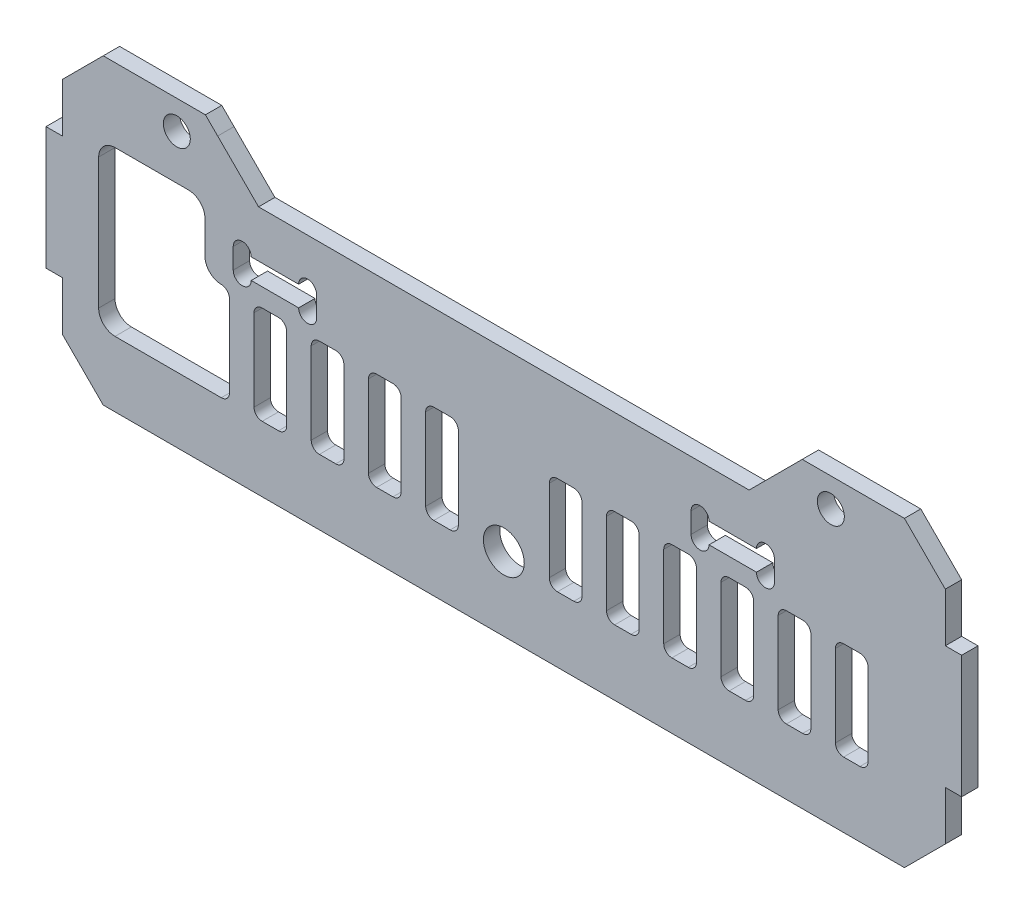
SolidWorks part; units mm, degrees
material "A-玻璃纤维"
ref_plane "前视基准面" through (0, 0, 0) normal (0, 0, 1) x (1, 0, 0)
ref_plane "上视基准面" through (0, 0, 0) normal (0, 1, 0) x (1, 0, 0)
ref_plane "右视基准面" through (0, 0, 0) normal (1, 0, 0) x (0, 0, -1)
sketch "草图1" plane through (0, 0, 0) normal (0, 0, 1) x (1, 0, 0)
  line L1 (52.5, -21.5) -> (-52.5, -21.5)
  line L2 (52.5, -21.5) -> (52.5, 21.5)
  line L3 (52.5, 21.5) -> (-52.5, 21.5)
  line L4 (-52.5, -21.5) -> (-52.5, 21.5)
  line L5 (52.5, -21.5) -> (-52.5, 21.5) construction
  line L6 (52.5, 21.5) -> (-52.5, -21.5) construction
  point P0 (0, 0)
  dimension "D1" = 43
  dimension "D2" = 105
extrude "凸台-拉伸1" add sketch "草图1" along normal blind 2
sketch "草图2" plane through (0, 0, 2) normal (0, 0, 1) x (1, 0, 0)
  line L0 (-52.5, -21.5) -> (52.5, -21.5) construction
  circle A0 centre (0, -6.5) radius 2.5
  dimension "D1" = 5
  dimension "D2" = 15
extrude "切除-拉伸1" cut sketch "草图2" against normal blind 2
sketch "草图3" plane through (0, 0, 2) normal (0, 0, 1) x (1, 0, 0)
  line L0 (0, -6.5) -> (0, 30.8618) construction
  line L1 (-52.5, -21.5) -> (52.5, -21.5) construction
  circle A0 centre (-40, -18.5) radius 1.65
  circle A1 centre (-40, 13.5) radius 1.65
  circle A2 centre (40, 13.5) radius 1.65
  circle A3 centre (40, -18.5) radius 1.65
  dimension "D1" = 3.3
  dimension "D2" = 3.3
  dimension "D4" = 32
  dimension "D5" = 3
  dimension "D3" = 40
extrude "切除-拉伸2" cut sketch "草图3" against normal blind 2
sketch "草图4" plane through (0, 0, 2) normal (0, 0, 1) x (1, 0, 0)
  line L0 (-2.5, -6.5) -> (2.5, -6.5) construction
  line L1 (-6.5592, -7.5) -> (-8.5592, -7.5)
  line L2 (-5.5592, -6.5) -> (-5.5592, 3.5)
  line L3 (-6.5592, 4.5) -> (-8.5592, 4.5)
  line L4 (-9.5592, -6.5) -> (-9.5592, 3.5)
  line L5 (-5.5592, -7.5) -> (-9.5592, 4.5) construction
  line L6 (-5.5592, 4.5) -> (-9.5592, -7.5) construction
  line L7 (-12.5592, -6.5) -> (-12.5592, 3.5)
  line L8 (-13.5592, -7.5) -> (-15.5592, -7.5)
  line L9 (-16.5592, -6.5) -> (-16.5592, 3.5)
  line L10 (-13.5592, 4.5) -> (-15.5592, 4.5)
  line L11 (-19.5592, -6.5) -> (-19.5592, 3.5)
  line L12 (-20.5592, -7.5) -> (-22.5592, -7.5)
  line L13 (-23.5592, -6.5) -> (-23.5592, 3.5)
  line L14 (-20.5592, 4.5) -> (-22.5592, 4.5)
  line L15 (-26.5592, -6.5) -> (-26.5592, 3.5)
  line L16 (-27.5592, -7.5) -> (-29.5592, -7.5)
  line L17 (-30.5592, -6.5) -> (-30.5592, 3.5)
  line L18 (-27.5592, 4.5) -> (-29.5592, 4.5)
  line L19 (-33.5592, -6.5) -> (-33.5592, 3.5)
  line L20 (-34.5592, -7.5) -> (-36.5592, -7.5)
  line L21 (-37.5592, -6.5) -> (-37.5592, 3.5)
  line L22 (-34.5592, 4.5) -> (-36.5592, 4.5)
  line L23 (-40.5592, -6.5) -> (-40.5592, 3.5)
  line L24 (-41.5592, -7.5) -> (-43.5592, -7.5)
  line L25 (-44.5592, -6.5) -> (-44.5592, 3.5)
  line L26 (-41.5592, 4.5) -> (-43.5592, 4.5)
  line L27 (0, -6.5) -> (0, 35.5966) construction
  line L28 (5.5592, 4.5) -> (9.5592, -7.5) construction
  line L29 (5.5592, -7.5) -> (9.5592, 4.5) construction
  line L30 (41.5592, 4.5) -> (43.5592, 4.5)
  line L31 (44.5592, -6.5) -> (44.5592, 3.5)
  line L32 (41.5592, -7.5) -> (43.5592, -7.5)
  line L33 (40.5592, -6.5) -> (40.5592, 3.5)
  line L34 (34.5592, 4.5) -> (36.5592, 4.5)
  line L35 (37.5592, -6.5) -> (37.5592, 3.5)
  line L36 (34.5592, -7.5) -> (36.5592, -7.5)
  line L37 (33.5592, -6.5) -> (33.5592, 3.5)
  line L38 (27.5592, 4.5) -> (29.5592, 4.5)
  line L39 (30.5592, -6.5) -> (30.5592, 3.5)
  line L40 (27.5592, -7.5) -> (29.5592, -7.5)
  line L41 (26.5592, -6.5) -> (26.5592, 3.5)
  line L42 (20.5592, 4.5) -> (22.5592, 4.5)
  line L43 (23.5592, -6.5) -> (23.5592, 3.5)
  line L44 (20.5592, -7.5) -> (22.5592, -7.5)
  line L45 (19.5592, -6.5) -> (19.5592, 3.5)
  line L46 (13.5592, 4.5) -> (15.5592, 4.5)
  line L47 (16.5592, -6.5) -> (16.5592, 3.5)
  line L48 (13.5592, -7.5) -> (15.5592, -7.5)
  line L49 (12.5592, -6.5) -> (12.5592, 3.5)
  line L50 (9.5592, -6.5) -> (9.5592, 3.5)
  line L51 (6.5592, 4.5) -> (8.5592, 4.5)
  line L52 (5.5592, -6.5) -> (5.5592, 3.5)
  line L53 (6.5592, -7.5) -> (8.5592, -7.5)
  circle A0 centre (0, -6.5) radius 2.5 construction
  arc A1 (-8.5592, -7.5) -> (-9.5592, -6.5) centre (-8.5592, -6.5) cw
  arc A2 (-6.5592, -7.5) -> (-5.5592, -6.5) centre (-6.5592, -6.5) ccw
  arc A3 (-5.5592, 3.5) -> (-6.5592, 4.5) centre (-6.5592, 3.5) ccw
  arc A4 (-8.5592, 4.5) -> (-9.5592, 3.5) centre (-8.5592, 3.5) ccw
  arc A5 (-12.5592, 3.5) -> (-13.5592, 4.5) centre (-13.5592, 3.5) ccw
  arc A6 (-13.5592, -7.5) -> (-12.5592, -6.5) centre (-13.5592, -6.5) ccw
  arc A7 (-15.5592, -7.5) -> (-16.5592, -6.5) centre (-15.5592, -6.5) cw
  arc A8 (-15.5592, 4.5) -> (-16.5592, 3.5) centre (-15.5592, 3.5) ccw
  arc A9 (-19.5592, 3.5) -> (-20.5592, 4.5) centre (-20.5592, 3.5) ccw
  arc A10 (-20.5592, -7.5) -> (-19.5592, -6.5) centre (-20.5592, -6.5) ccw
  arc A11 (-22.5592, -7.5) -> (-23.5592, -6.5) centre (-22.5592, -6.5) cw
  arc A12 (-22.5592, 4.5) -> (-23.5592, 3.5) centre (-22.5592, 3.5) ccw
  arc A13 (-26.5592, 3.5) -> (-27.5592, 4.5) centre (-27.5592, 3.5) ccw
  arc A14 (-27.5592, -7.5) -> (-26.5592, -6.5) centre (-27.5592, -6.5) ccw
  arc A15 (-29.5592, -7.5) -> (-30.5592, -6.5) centre (-29.5592, -6.5) cw
  arc A16 (-29.5592, 4.5) -> (-30.5592, 3.5) centre (-29.5592, 3.5) ccw
  arc A17 (-33.5592, 3.5) -> (-34.5592, 4.5) centre (-34.5592, 3.5) ccw
  arc A18 (-34.5592, -7.5) -> (-33.5592, -6.5) centre (-34.5592, -6.5) ccw
  arc A19 (-36.5592, -7.5) -> (-37.5592, -6.5) centre (-36.5592, -6.5) cw
  arc A20 (-36.5592, 4.5) -> (-37.5592, 3.5) centre (-36.5592, 3.5) ccw
  arc A21 (-40.5592, 3.5) -> (-41.5592, 4.5) centre (-41.5592, 3.5) ccw
  arc A22 (-41.5592, -7.5) -> (-40.5592, -6.5) centre (-41.5592, -6.5) ccw
  arc A23 (-43.5592, -7.5) -> (-44.5592, -6.5) centre (-43.5592, -6.5) cw
  arc A24 (-43.5592, 4.5) -> (-44.5592, 3.5) centre (-43.5592, 3.5) ccw
  arc A25 (43.5592, 4.5) -> (44.5592, 3.5) centre (43.5592, 3.5) cw
  arc A26 (43.5592, -7.5) -> (44.5592, -6.5) centre (43.5592, -6.5) ccw
  arc A27 (41.5592, -7.5) -> (40.5592, -6.5) centre (41.5592, -6.5) cw
  arc A28 (40.5592, 3.5) -> (41.5592, 4.5) centre (41.5592, 3.5) cw
  arc A29 (36.5592, 4.5) -> (37.5592, 3.5) centre (36.5592, 3.5) cw
  arc A30 (36.5592, -7.5) -> (37.5592, -6.5) centre (36.5592, -6.5) ccw
  arc A31 (34.5592, -7.5) -> (33.5592, -6.5) centre (34.5592, -6.5) cw
  arc A32 (33.5592, 3.5) -> (34.5592, 4.5) centre (34.5592, 3.5) cw
  arc A33 (29.5592, 4.5) -> (30.5592, 3.5) centre (29.5592, 3.5) cw
  arc A34 (29.5592, -7.5) -> (30.5592, -6.5) centre (29.5592, -6.5) ccw
  arc A35 (27.5592, -7.5) -> (26.5592, -6.5) centre (27.5592, -6.5) cw
  arc A36 (26.5592, 3.5) -> (27.5592, 4.5) centre (27.5592, 3.5) cw
  arc A37 (22.5592, 4.5) -> (23.5592, 3.5) centre (22.5592, 3.5) cw
  arc A38 (22.5592, -7.5) -> (23.5592, -6.5) centre (22.5592, -6.5) ccw
  arc A39 (20.5592, -7.5) -> (19.5592, -6.5) centre (20.5592, -6.5) cw
  arc A40 (19.5592, 3.5) -> (20.5592, 4.5) centre (20.5592, 3.5) cw
  arc A41 (15.5592, 4.5) -> (16.5592, 3.5) centre (15.5592, 3.5) cw
  arc A42 (15.5592, -7.5) -> (16.5592, -6.5) centre (15.5592, -6.5) ccw
  arc A43 (13.5592, -7.5) -> (12.5592, -6.5) centre (13.5592, -6.5) cw
  arc A44 (12.5592, 3.5) -> (13.5592, 4.5) centre (13.5592, 3.5) cw
  arc A45 (8.5592, 4.5) -> (9.5592, 3.5) centre (8.5592, 3.5) cw
  arc A46 (5.5592, 3.5) -> (6.5592, 4.5) centre (6.5592, 3.5) cw
  arc A47 (6.5592, -7.5) -> (5.5592, -6.5) centre (6.5592, -6.5) cw
  arc A48 (8.5592, -7.5) -> (9.5592, -6.5) centre (8.5592, -6.5) ccw
  point P0 (-7.5592, -1.5)
  point P161 (7.5592, -1.5)
  dimension "D5" = 1
  dimension "D1" = 12
  dimension "D2" = 4
  dimension "D3" = 4
  dimension "D4" = 5
  dimension "D6" = 6
extrude "切除-拉伸3" cut sketch "草图4" against normal blind 2
sketch "草图5" plane through (0, 0, 2) normal (0, 0, 1) x (1, 0, 0)
  line L0 (-28, 8) -> (-28, 13.9357) construction
  line L1 (-25.1, 6.75) -> (-30.9, 6.75)
  line L2 (-22.9, 6.75) -> (-22.9, 9.25)
  line L3 (-25.1, 9.25) -> (-30.9, 9.25)
  line L4 (-33.1, 6.75) -> (-33.1, 9.25)
  line L5 (-22.9, 6.75) -> (-33.1, 9.25) construction
  line L6 (-22.9, 9.25) -> (-33.1, 6.75) construction
  line L11 (0, 0) -> (0, 36.2571) construction
  line L12 (22.9, 6.75) -> (22.9, 9.25)
  line L13 (25.1, 9.25) -> (30.9, 9.25)
  line L14 (33.1, 6.75) -> (33.1, 9.25)
  line L15 (25.1, 6.75) -> (30.9, 6.75)
  arc A0 (-30.9, 9.25) -> (-33.1, 9.25) centre (-32, 9.25) ccw
  arc A1 (-33.1, 6.75) -> (-30.9, 6.75) centre (-32, 6.75) ccw
  arc A2 (-22.9, 6.75) -> (-25.1, 6.75) centre (-24, 6.75) cw
  arc A3 (-25.1, 9.25) -> (-22.9, 9.25) centre (-24, 9.25) cw
  arc A4 (22.9, 6.75) -> (25.1, 6.75) centre (24, 6.75) ccw
  arc A5 (25.1, 9.25) -> (22.9, 9.25) centre (24, 9.25) ccw
  arc A6 (30.9, 9.25) -> (33.1, 9.25) centre (32, 9.25) cw
  arc A7 (33.1, 6.75) -> (30.9, 6.75) centre (32, 6.75) cw
  point P0 (-28, 8)
  point P5 (28, 8)
  dimension "D8" = 2.2
  dimension "D9" = 2.2
  dimension "D1" = 2.5
  dimension "D2" = 10.2
  dimension "D5" = 28
  dimension "D6" = 28
  dimension "D7" = 8
extrude "切除-拉伸4" cut sketch "草图5" against normal blind 2
sketch "草图6" plane through (0, 0, 2) normal (0, 0, 1) x (1, 0, 0)
  line L0 (-52.5, 21.5) -> (-52.5, -21.5) construction
  line L1 (52.5, -21.5) -> (52.5, 21.5) construction
  line L2 (-52.5, -21.5) -> (52.5, -21.5) construction
  circle A0 centre (-49.5, 3.5) radius 1.65
  circle A1 centre (-49.5, -11.5) radius 1.65
  circle A2 centre (49.5, 3.5) radius 1.65
  circle A3 centre (49.5, -11.5) radius 1.65
  dimension "D1" = 3.3
  dimension "D2" = 3.3
  dimension "D3" = 3.3
  dimension "D4" = 3.3
  dimension "D5" = 3
  dimension "D6" = 3
  dimension "D7" = 15
  dimension "D8" = 10
sketch "草图7" plane through (0, 0, 2) normal (0, 0, 1) x (1, 0, 0)
  line L0 (52.5, 21.5) -> (-52.5, 21.5) construction
  line L1 (-53.8951, 21.5) -> (65.5252, 21.5)
  line L2 (-53.8951, 21.5) -> (-53.8951, 11.5)
  line L3 (-53.8951, 11.5) -> (65.5252, 11.5)
  line L4 (65.5252, 21.5) -> (65.5252, 11.5)
  dimension "D1" = 10
extrude "切除-拉伸6" cut sketch "草图7" against normal blind 2
sketch "草图8" plane through (0, 0, 2) normal (0, 0, 1) x (1, 0, 0)
  line L1 (-52.5, 11.5) -> (-48.39, 11.5)
  line L2 (-52.5, 11.5) -> (-52.5, -21.5)
  line L3 (-52.5, -21.5) -> (-48.39, -21.5)
  line L4 (-48.39, 11.5) -> (-48.39, -21.5)
  line L5 (-52.5, -21.5) -> (52.5, -21.5) construction
  line L7 (52.5, 11.5) -> (48.39, 11.5)
  line L8 (52.5, 11.5) -> (52.5, -21.5)
  line L9 (52.5, -21.5) -> (48.39, -21.5)
  line L10 (48.39, 11.5) -> (48.39, -21.5)
  dimension "D1" = 33
  dimension "D2" = 4.11
  dimension "D3" = 33
  dimension "D4" = 4.11
extrude "切除-拉伸7" cut sketch "草图8" against normal blind 2
sketch "草图11" plane through (0, 0, 2) normal (0, 0, 1) x (1, 0, 0)
  line L0 (-48.39, -21.5) -> (-48.39, 11.5) construction
  line L1 (-48.39, 8.5) -> (-50.39, 8.5)
  line L2 (-48.39, 8.5) -> (-48.39, -6.5)
  line L3 (-48.39, -6.5) -> (-50.39, -6.5)
  line L4 (-50.39, 8.5) -> (-50.39, -6.5)
  line L5 (48.39, 11.5) -> (48.39, -21.5) construction
  line L6 (48.39, 8.5) -> (50.39, 8.5)
  line L7 (48.39, 8.5) -> (48.39, -6.5)
  line L8 (48.39, -6.5) -> (50.39, -6.5)
  line L9 (50.39, 8.5) -> (50.39, -6.5)
  line L10 (-48.39, 11.5) -> (48.39, 11.5) construction
  dimension "D1" = 15
  dimension "D2" = 2
  dimension "D3" = 15
  dimension "D4" = 2
  dimension "D9" = 3
  dimension "D11" = 3
extrude "凸台-拉伸2" add sketch "草图11" against normal up to vertex (2 mm away) up to point (22.9, 9.25, 0)
sketch "草图13" plane through (0, 0, 0) normal (0, 0, -1) x (-1, 0, 0)
  line L0 (48.39, -21.5) -> (48.39, -6.5) construction
  line L1 (-48.39, -21.5) -> (48.39, -21.5)
  line L2 (-48.39, -21.5) -> (-48.39, -15.5)
  line L3 (-48.39, -15.5) -> (48.39, -15.5)
  line L4 (48.39, -21.5) -> (48.39, -15.5)
  dimension "D1" = 6
extrude "切除-拉伸8" cut sketch "草图13" against normal blind 2
sketch "草图14" plane through (0, 0, 0) normal (0, 0, -1) x (-1, 0, 0)
  line L0 (48.39, 11.5) -> (-48.39, 11.5) construction
  line L1 (48.39, 21.5) -> (-48.39, 21.5)
  line L2 (48.39, 21.5) -> (48.39, 11.5)
  line L3 (48.39, 11.5) -> (-48.39, 11.5)
  line L4 (-48.39, 21.5) -> (-48.39, 11.5)
  line L5 (48.39, 21.5) -> (-48.39, 11.5) construction
  line L6 (48.39, 11.5) -> (-48.39, 21.5) construction
  line L7 (-48.39, 11.5) -> (-48.39, 8.5) construction
  point P0 (0, 16.5)
  dimension "D1" = 10
extrude "凸台-拉伸3" add sketch "草图14" against normal up to surface (2 mm away) up to face at (0, 0, 2)
sketch "草图15" plane through (0, 0, 0) normal (0, 0, -1) x (-1, 0, 0)
  circle A0 centre (-40, 18) radius 1.65
  circle A1 centre (40, 18) radius 1.65
  dimension "D1" = 3.3
  dimension "D2" = 3.3
  dimension "D3" = 40
  dimension "D4" = 18
  dimension "D5" = 40
extrude "切除-拉伸9" cut sketch "草图15" against normal blind 10
sketch "草图17" plane through (0, 0, 0) normal (0, 0, -1) x (-1, 0, 0)
  line L0 (48.39, 21.5) -> (-48.39, 21.5) construction
  line L1 (35, 28) -> (-35, 28)
  line L2 (35, 28) -> (35, 15)
  line L3 (35, 15) -> (-35, 15)
  line L4 (-35, 28) -> (-35, 15)
  line L5 (35, 28) -> (-35, 15) construction
  line L6 (35, 15) -> (-35, 28) construction
  point P0 (0, 21.5)
  dimension "D1" = 13
  dimension "D2" = 70
extrude "切除-拉伸10" cut sketch "草图17" against normal blind 50
sketch "草图18" plane through (-48.39, 0, 0) normal (-1, 0, 0) x (0, 0, 1)
  line L4 (0, 21.5) -> (0, 8.5)
  line L5 (0, 8.5) -> (2, 8.5)
  line L6 (2, 8.5) -> (2, 21.5)
  line L7 (2, 21.5) -> (0, 21.5)
  line L8 (0, 21.5) -> (0, 8.5)
  line L9 (0, 8.5) -> (2, 8.5)
  line L10 (2, 8.5) -> (2, 21.5)
  line L11 (2, 21.5) -> (0, 21.5)
  line L12 (0, -6.5) -> (0, -15.5)
  line L13 (0, -15.5) -> (2, -15.5)
  line L14 (2, -15.5) -> (2, -6.5)
  line L15 (2, -6.5) -> (0, -6.5)
  line L16 (0, -6.5) -> (0, -15.5)
  line L17 (0, -15.5) -> (2, -15.5)
  line L18 (2, -15.5) -> (2, -6.5)
  line L19 (2, -6.5) -> (0, -6.5)
  dimension "D1" = 0
  dimension "D2" = 0
extrude "凸台-拉伸4" add sketch "草图18" along normal up to surface (2 mm away) up to face at (-50.39, 1, 1)
sketch "草图19" plane through (48.39, 0, 0) normal (1, 0, 0) x (0, 0, -1)
  line L4 (-2, 8.5) -> (0, 8.5)
  line L5 (0, 8.5) -> (0, 21.5)
  line L6 (0, 21.5) -> (-2, 21.5)
  line L7 (-2, 21.5) -> (-2, 8.5)
  line L8 (-2, 8.5) -> (0, 8.5)
  line L9 (0, 8.5) -> (0, 21.5)
  line L10 (0, 21.5) -> (-2, 21.5)
  line L11 (-2, 21.5) -> (-2, 8.5)
  line L12 (-2, -6.5) -> (-2, -15.5)
  line L13 (-2, -15.5) -> (0, -15.5)
  line L14 (0, -15.5) -> (0, -6.5)
  line L15 (0, -6.5) -> (-2, -6.5)
  line L16 (-2, -6.5) -> (-2, -15.5)
  line L17 (-2, -15.5) -> (0, -15.5)
  line L18 (0, -15.5) -> (0, -6.5)
  line L19 (0, -6.5) -> (-2, -6.5)
  dimension "D1" = 0
  dimension "D2" = 0
extrude "凸台-拉伸5" add sketch "草图19" along normal up to surface (2 mm away) up to face at (50.39, 1, 1)
sketch "草图20" plane through (0, 0, 2) normal (0, 0, 1) x (1, 0, 0)
  line L1 (-50.39, 21.5) -> (-54, 21.5)
  line L2 (-50.39, 21.5) -> (-50.39, -15.5)
  line L3 (-50.39, -15.5) -> (-54, -15.5)
  line L4 (-54, 21.5) -> (-54, -15.5)
  line L5 (50.39, 21.5) -> (54, 21.5)
  line L6 (50.39, 21.5) -> (50.39, -15.5)
  line L7 (50.39, -15.5) -> (54, -15.5)
  line L8 (54, 21.5) -> (54, -15.5)
  dimension "D1" = 37
  dimension "D2" = 3.61
  dimension "D3" = 37
  dimension "D4" = 3.61
extrude "凸台-拉伸6" add sketch "草图20" against normal up to surface (2 mm away) up to face at (0, 10.625, 0)
sketch "草图21" plane through (0, 0, 2) normal (0, 0, 1) x (1, 0, 0)
  line L0 (-54, 21.5) -> (-54, -15.5) construction
  line L1 (-52, -4.5) -> (-56, -4.5)
  line L2 (-52, -4.5) -> (-52, 10.5)
  line L3 (-52, 10.5) -> (-56, 10.5)
  line L4 (-56, -4.5) -> (-56, 10.5)
  line L5 (-52, -4.5) -> (-56, 10.5) construction
  line L6 (-52, 10.5) -> (-56, -4.5) construction
  line L7 (54, -15.5) -> (54, 21.5) construction
  line L8 (56, -4.5) -> (52, -4.5)
  line L9 (56, -4.5) -> (56, 10.5)
  line L10 (56, 10.5) -> (52, 10.5)
  line L11 (52, -4.5) -> (52, 10.5)
  line L12 (56, -4.5) -> (52, 10.5) construction
  line L13 (56, 10.5) -> (52, -4.5) construction
  point P0 (-54, 3)
  point P7 (54, 3)
  dimension "D1" = 15
  dimension "D2" = 4
  dimension "D3" = 15
  dimension "D4" = 4
extrude "凸台-拉伸7" add sketch "草图21" against normal up to surface (2 mm away) up to face at (0, 10.625, 0)
chamfer "倒角1" distance 5 angle 45 6 edges at (-54, 21.5, 1) (-35, 15, 1) (35, 15, 1) (54, 21.5, 1) (54, -15.5, 1) (-54, -15.5, 1)
chamfer "倒角2" distance 1.5 angle 45 2 edges at (35, 21.5, 1) (-35, 21.5, 1)
sketch "草图23" plane through (0, 0, 2) normal (0, 0, 1) x (1, 0, 0)
  line L1 (-36.5592, -7.5) -> (-49.5592, -7.5)
  line L2 (-36.5592, -7.5) -> (-36.5592, 12.5)
  line L3 (-36.5592, 12.5) -> (-49.5592, 12.5)
  line L4 (-49.5592, -7.5) -> (-49.5592, 12.5)
  dimension "D1" = 20
  dimension "D2" = 13
extrude "切除-拉伸12" cut sketch "草图23" against normal blind 10
fillet "圆角2" radius 2 4 edges at (-49.5592, -7.5, 1) (-49.5592, 12.5, 1) (-36.5592, 12.5, 1) (-36.5592, 4.5, 1)
